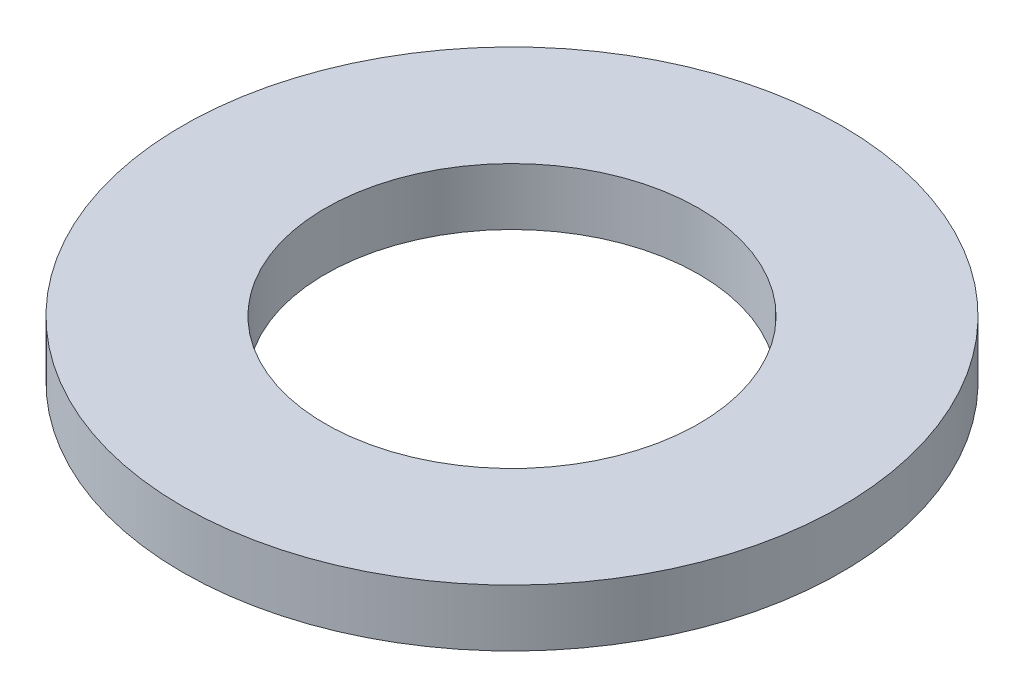
SolidWorks part; units mm, degrees
ref_plane "Front Plane" through (0, 0, 0) normal (0, 0, 1) x (1, 0, 0)
ref_plane "Top Plane" through (0, 0, 0) normal (0, 1, 0) x (1, 0, 0)
ref_plane "Right Plane" through (0, 0, 0) normal (1, 0, 0) x (0, 0, -1)
sketch "Sketch1" plane through (0, 0, 0) normal (0, 1, 0) x (1, 0, 0)
  circle A0 centre (0, 0) radius 75
  dimension "FLANGE_OD" = 150
extrude "Boss-Extrude1" add sketch "Sketch1" along normal blind 13
sketch "Sketch2" plane through (0, 0, 0) normal (0, 1, 0) x (1, 0, 0)
  circle A0 centre (0, 0) radius 42.5
  dimension "BORE_D" = 85
extrude "Cut-Extrude1" cut sketch "Sketch2" along normal through all
sketch "Sketch3" plane through (0, 13, 0) normal (0, 1, 0) x (1, 0, 0)
  circle A0 centre (0, 0) radius 26.3295 construction
  circle A1 centre (-26.3295, 0) radius 2.9328
  dimension "BOLT_D" = 5.8657
  dimension "BOLT_PCD" = 52.6591
extrude "Cut-Extrude2" cut sketch "Sketch3" against normal blind 10.15 rebuild error yes
pattern_circular "CirPattern1" count 5 over 360 rebuild error yes
